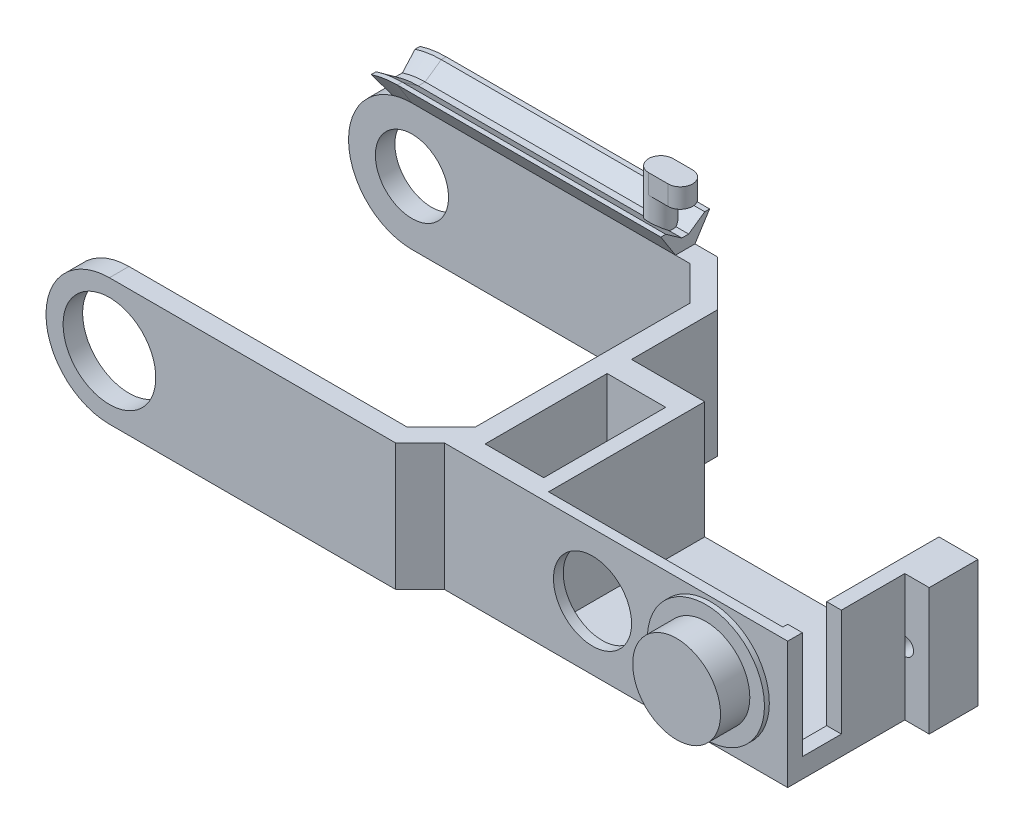
SolidWorks part; units mm, degrees
material "uhlíková ocel 7850"
ref_plane "Přední rovina" through (0, 0, 0) normal (0, 0, 1) x (1, 0, 0)
ref_plane "Horní rovina" through (0, 0, 0) normal (0, 1, 0) x (1, 0, 0)
ref_plane "Pravá rovina" through (0, 0, 0) normal (1, 0, 0) x (0, 0, -1)
sketch "Skica1" plane through (0, 0, 0) normal (0, 1, 0) x (1, 0, 0)
  line L0 (0, -11) -> (0, 11)
  line L1 (0, 11) -> (-3.5, 14.5)
  line L2 (-3.5, 14.5) -> (-38.5, 14.5)
  line L3 (-38.5, 14.5) -> (-38.5, 16.5)
  line L4 (-38.5, 16.5) -> (-2.6716, 16.5)
  line L5 (-2.6716, 16.5) -> (2, 11.8284)
  line L6 (2, 11.8284) -> (2, -11.8284)
  line L7 (2, 0) -> (0, 0) construction
  line L8 (-2.6716, -16.5) -> (2, -11.8284)
  line L9 (-38.5, -16.5) -> (-2.6716, -16.5)
  line L10 (-38.5, -14.5) -> (-38.5, -16.5)
  line L11 (-3.5, -14.5) -> (-38.5, -14.5)
  line L12 (0, -11) -> (-3.5, -14.5)
  dimension "D1" = 11
  dimension "D2" = 135
  dimension "D3" = 35
  dimension "D4" = 2
  dimension "D5" = 2
  dimension "D6" = 2
  dimension "D7" = 14.5
extrude "Přidat vysunutím1" add sketch "Skica1" along normal blind 13
sketch "Skica2" plane through (0, 0, 0) normal (0, -1, 0) x (1, 0, 0)
  line L0 (-0.1716, 14) -> (35, 14)
  line L1 (-2.6716, 16.5) -> (2, 11.8284) construction
  line L2 (35, 14) -> (35, 2)
  line L3 (35, 2) -> (37.5, 2)
  line L4 (37.5, 2) -> (37.5, -3)
  line L5 (37.5, -3) -> (2, -3)
  line L6 (2, 11.8284) -> (2, -11.8284) construction
  line L7 (2, -3) -> (2, 11.8284)
  line L8 (2, 11.8284) -> (-0.1716, 14)
  line L9 (-38.5, 16.5) -> (-2.6716, 16.5) construction
  line L10 (0, -11) -> (0, 11) construction
  dimension "D1" = 2.5
  dimension "D2" = 35
  dimension "D3" = 12
  dimension "D4" = 5
  dimension "D5" = 2.5
extrude "Přidat vysunutím2" add sketch "Skica2" against normal up to surface (13 mm away) up to face at (-13.5286, 13, 0)
sketch "Skica3" plane through (0, 13, 0) normal (0, 1, 0) x (1, 0, 0)
  line L0 (0, 11) -> (0, -11) construction
  line L1 (2, 0.5) -> (8, 0.5)
  line L2 (2, 0.5) -> (2, -12)
  line L3 (2, -12) -> (8, -12)
  line L4 (8, 0.5) -> (8, -12)
  line L5 (37.5, 3) -> (2, 3) construction
  line L6 (-0.1716, -14) -> (35, -14) construction
  dimension "D1" = 2
  dimension "D2" = 2.5
  dimension "D3" = 2
  dimension "D4" = 6
extrude "Odebrat vysunutím1" cut sketch "Skica3" against normal through all
sketch "Skica4" plane through (0, 13, 0) normal (0, 1, 0) x (1, 0, 0)
  line L0 (37.5, 3) -> (2, 3) construction
  line L1 (9.5, 3) -> (33.5, 3)
  line L2 (9.5, 3) -> (9.5, -13)
  line L3 (9.5, -13) -> (33.5, -13)
  line L4 (33.5, 3) -> (33.5, -13)
  line L5 (-0.1716, -14) -> (35, -14) construction
  line L6 (35, -14) -> (35, -2) construction
  dimension "D1" = 1
  dimension "D2" = 1.5
  dimension "D3" = 24
extrude "Odebrat vysunutím2" cut sketch "Skica4" against normal blind 12
sketch "Skica5" plane through (0, 0, -3) normal (0, 0, -1) x (-1, 0, 0)
  circle A0 centre (-34.9938, 6.5551) radius 1.1906 construction
  circle A1 centre (-8.0063, 6.5551) radius 1.1906 construction
  circle A2 centre (-34.9938, 6.5551) radius 0.9
  circle A3 centre (-8.0063, 6.5551) radius 0.9
  dimension "D1" = 1.8
extrude "Odebrat vysunutím3" cut sketch "Skica5" against normal blind 5 contours A1 | A2 | A3 region at (34.9938, 6.5551, -3) region at (8.0063, 6.5551, -3)
fillet "Zaoblit1" radius 6.5 4 edges at (-38.5, 0, -15.5) (-38.5, 0, 15.5) (-38.5, 13, 15.5) (-38.5, 13, -15.5)
sketch "Skica6" plane through (0, 0, -16.5) normal (0, 0, -1) x (-1, 0, 0)
  circle A0 centre (32, 6.5) radius 3.75
  dimension "D1" = 7.5
extrude "Odebrat vysunutím4" cut sketch "Skica6" against normal blind 5
sketch "Skica7" plane through (0, 0, 14.5) normal (0, 0, -1) x (-1, 0, 0)
  circle A0 centre (32, 6.5) radius 4.75
  dimension "D1" = 9.5
extrude "Odebrat vysunutím5" cut sketch "Skica7" against normal blind 5
sketch "Skica8" plane through (35, 0, 0) normal (1, 0, 0) x (0, 0, -1)
  line L0 (-14, 13) -> (-2, 13) construction
  line L1 (-12.5, 13) -> (-8.5, 13)
  line L2 (-12.5, 13) -> (-12.5, 2)
  line L3 (-12.5, 2) -> (-8.5, 2)
  line L4 (-8.5, 13) -> (-8.5, 2)
  line L5 (-14, 13) -> (-14, 0) construction
  dimension "D1" = 1.5
  dimension "D2" = 4
  dimension "D3" = 11
extrude "Odebrat vysunutím6" cut sketch "Skica8" against normal blind 5
sketch "Skica9" plane through (0, 0, 14) normal (0, 0, 1) x (1, 0, 0)
  line L0 (-22.25, 6.555) -> (27.1188, 6.555) construction
  line L3 (35, 13) -> (35, 0) construction
  circle A0 centre (15, 6.555) radius 4
  dimension "D1" = 8
  dimension "D2" = 20
extrude "Odebrat vysunutím7" cut sketch "Skica9" against normal blind 10
sketch "Skica10" plane through (0, 0, 14) normal (0, 0, 1) x (1, 0, 0)
  circle A0 centre (27.1188, 6.555) radius 6
  dimension "D1" = 12
extrude "Přidat vysunutím3" add sketch "Skica10" along normal blind 0.5
sketch "Skica11" plane through (0, 0, 14.5) normal (0, 0, 1) x (1, 0, 0)
  circle A0 centre (27.1188, 6.555) radius 4.5
  dimension "D1" = 9
extrude "Přidat vysunutím4" add sketch "Skica11" along normal blind 3
ref_plane "Rovina1" through (-5, 0, 0) normal (-1, 0, 0) x (0, 0, 1)
sketch "Skica12" plane through (-5, 0, 0) normal (-1, 0, 0) x (0, 0, 1)
  line L0 (-15.5, 13) -> (-15.5, 17.8474) construction
  line L1 (-16.5, 13) -> (-14.5, 13) construction
  line L2 (-14.5, 13) -> (-16.5, 13)
  line L3 (-16.5, 13) -> (-18, 15.3545)
  line L4 (-18, 15.3545) -> (-17.5, 15.3545)
  line L5 (-17.5, 15.3545) -> (-15.8512, 14.2)
  line L6 (-15.8512, 14.2) -> (-15.1488, 14.2)
  line L7 (-13.5, 15.3545) -> (-15.1488, 14.2)
  line L8 (-13, 15.3545) -> (-13.5, 15.3545)
  line L9 (-14.5, 13) -> (-13, 15.3545)
  point P11 (-15.5, 14.2)
  dimension "D1" = 1.2
  dimension "D2" = 5
  dimension "D3" = 65
  dimension "D4" = 110
  dimension "D5" = 0.5
sketch "Skica14" plane through (0, 0, -16.5) normal (0, 0, -1) x (-1, 0, 0)
  line L0 (2.6716, 13) -> (32, 13) construction
  line L1 (5, 13) -> (32, 13)
  arc A0 (38.5, 6.5) -> (32, 13) centre (32, 6.5) ccw construction
  arc A1 (33.9686, 12.6947) -> (32, 13) centre (32, 6.5) ccw
  dimension "D1" = 2
sweep "Táhnout po křivce1" add profiles "Skica12" path "Skica14"
sketch "Skica15" plane through (0, 14.2, 0) normal (0, 1, 0) x (1, 0, 0)
  line L0 (-5, 15.1488) -> (-5, 15.8512) construction
  line L1 (-7.5, 15.5) -> (-5, 15.5) construction
  line L2 (-5, 16.5) -> (-5, 14.5) construction
  circle A0 centre (-7.5, 15.5) radius 1.25
  dimension "D1" = 2.5
  dimension "D2" = 2.5
extrude "Přidat vysunutím5" add sketch "Skica15" against normal up to body from offset 3
sketch "Skica16" plane through (0, 17.2, 0) normal (0, 1, 0) x (1, 0, 0)
  line L0 (-7.5, 15.5) -> (-5.5, 15.5) construction
  line L1 (-7.5, 16.75) -> (-5.5, 16.75)
  line L2 (-7.5, 14.25) -> (-5.5, 14.25)
  arc A0 (-7.5, 16.75) -> (-7.5, 14.25) centre (-7.5, 15.5) ccw
  arc A1 (-5.5, 14.25) -> (-5.5, 16.75) centre (-5.5, 15.5) ccw
  arc A2 (-6.3003, 15.8512) -> (-8.6997, 15.8512) centre (-7.5, 15.5) ccw construction
  point P3 (-6.5, 15.5)
  dimension "D1" = 2
extrude "Přidat vysunutím6" add sketch "Skica16" along normal blind 2
